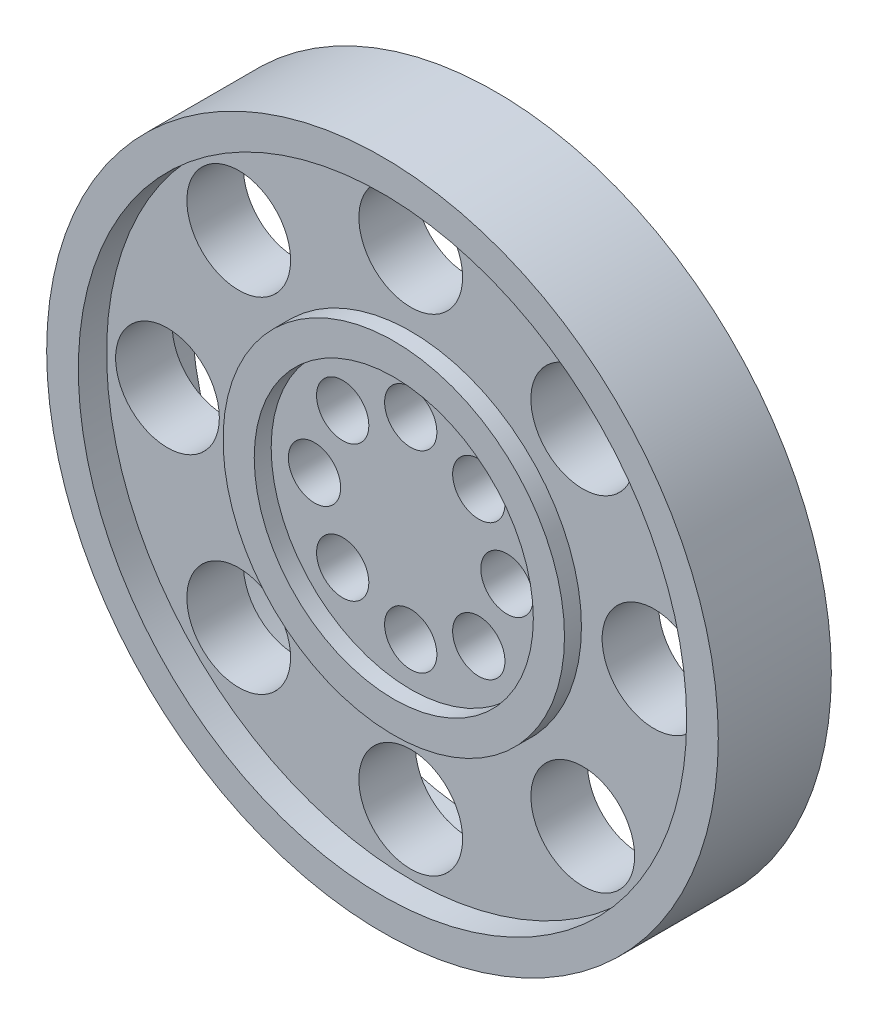
SolidWorks part; units mm, degrees
ref_plane "Front Plane" through (0, 0, 0) normal (0, 0, 1) x (1, 0, 0)
ref_plane "Top Plane" through (0, 0, 0) normal (0, 1, 0) x (1, 0, 0)
ref_plane "Right Plane" through (0, 0, 0) normal (1, 0, 0) x (0, 0, -1)
sketch "Sketch1" plane through (0, 0, 0) normal (0, 0, 1) x (1, 0, 0)
  line L0 (0, 59.41) -> (0, 52.21) construction
  circle A0 centre (0, 0) radius 59.41
  circle A1 centre (0, 0) radius 53.81
  circle A2 centre (0, 0) radius 5.35
  circle A3 centre (0, 0) radius 30.2
  circle A4 centre (0, 0) radius 24.69
  circle A5 centre (0, 17.0241) radius 4.625
  circle A6 centre (0, 43.035) radius 9.175
  point P13 (0, 0)
  dimension "D1" = 118.82
  dimension "D2" = 60.4
  dimension "D3" = 18.35
  dimension "D4" = 9.25
  dimension "D5" = 10.7
  dimension "D6" = 5.51
  dimension "D7" = 5.6
  dimension "D8" = 7.2
extrude "Boss-Extrude1" add sketch "Sketch1" along normal mid plane 20 contours A0 A1 region at (-57.7296, 0, 0)
extrude "Boss-Extrude2" add sketch "Sketch1<3>" along normal mid plane 10 contours A1 A6 A3 | A4 region at (-52.288, 0, 0)
sketch "Sketch1<3>" plane through (0, 0, 0) normal (0, 0, 1) x (1, 0, 0) same geometry as "Sketch1"
extrude "Boss-Extrude3" add sketch "Sketch1<4>" along normal mid plane 16 contours A3 A4 region at (-29.3458, 0, 0)
sketch "Sketch1<4>" plane through (0, 0, 0) normal (0, 0, 1) x (1, 0, 0) same geometry as "Sketch1"
extrude "Cut-Extrude1" cut sketch "Sketch1<5>" against normal through all both and the other way through all contours A5 | A6
sketch "Sketch1<5>" plane through (0, 0, 0) normal (0, 0, 1) x (1, 0, 0) same geometry as "Sketch1"
pattern_circular "CirPattern2" count 8 over 360 about axis through (0, 0, 8) along (0, 0, 1) of "Cut-Extrude1"
